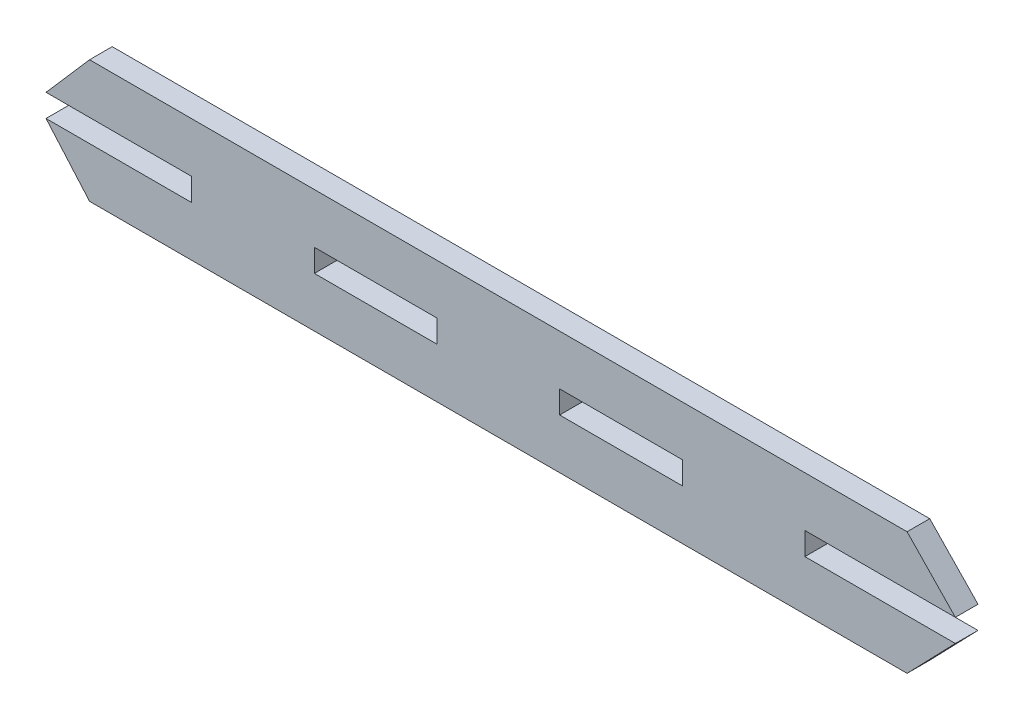
SolidWorks part; units mm, degrees
ref_plane "Front Plane" through (0, 0, 0) normal (0, 0, 1) x (1, 0, 0)
ref_plane "Top Plane" through (0, 0, 0) normal (0, 1, 0) x (1, 0, 0)
ref_plane "Right Plane" through (0, 0, 0) normal (1, 0, 0) x (0, 0, -1)
sketch "Sketch2" plane through (0, 0, 0) normal (0, 0, 1) x (1, 0, 0)
  line L5 (70.8837, 21.3653) -> (270.8837, 21.3653)
  line L35 (170.8837, 21.3653) -> (170.8837, 6.3653) construction
  line L40 (70.8837, -8.6347) -> (270.8837, -8.6347)
  line L42 (185.8837, 9.1353) -> (215.8837, 9.1353)
  line L43 (185.8837, 9.1353) -> (185.8837, 3.5953)
  line L44 (185.8837, 3.5953) -> (215.8837, 3.5953)
  line L45 (215.8837, 9.1353) -> (215.8837, 3.5953)
  line L57 (60.2283, 9.1353) -> (70.8837, 21.3653)
  line L58 (60.2283, 3.5953) -> (70.8837, -8.6347)
  line L59 (270.8837, -8.6347) -> (282.6872, 3.5953)
  line L60 (270.8837, 21.3653) -> (282.6872, 9.1353)
  line L62 (125.8837, 9.1353) -> (125.8837, 3.5953)
  line L63 (125.8837, 9.1353) -> (155.8837, 9.1353)
  line L64 (155.8837, 9.1353) -> (155.8837, 3.5953)
  line L65 (125.8837, 3.5953) -> (155.8837, 3.5953)
  line L67 (60.2283, 3.5953) -> (95.8837, 3.5953)
  line L69 (60.2283, 9.1353) -> (95.8837, 9.1353)
  line L70 (95.8837, 3.5953) -> (95.8837, 9.1353)
  line L71 (282.6872, 3.5953) -> (245.8837, 3.5953)
  line L73 (282.6872, 9.1353) -> (245.8837, 9.1353)
  line L74 (245.8837, 3.5953) -> (245.8837, 9.1353)
  point P0 (0, 0)
  point P12 (170.8837, 13.8653)
  dimension "D2" = 5.54
  dimension "D3" = 0
  dimension "D4" = 5.54
  dimension "D5" = 30
  dimension "D6" = 15
  dimension "D8" = 2
  dimension "D14" = 30
  dimension "D9" = 30
  dimension "D10" = 15
  dimension "D11" = 30
  dimension "D12" = 200
  dimension "D7" = 30
  dimension "D13" = 5.54
  dimension "D15" = 12.23
  dimension "D16" = 12.23
extrude "Boss-Extrude1" add sketch "Sketch2" along normal blind 5.54
